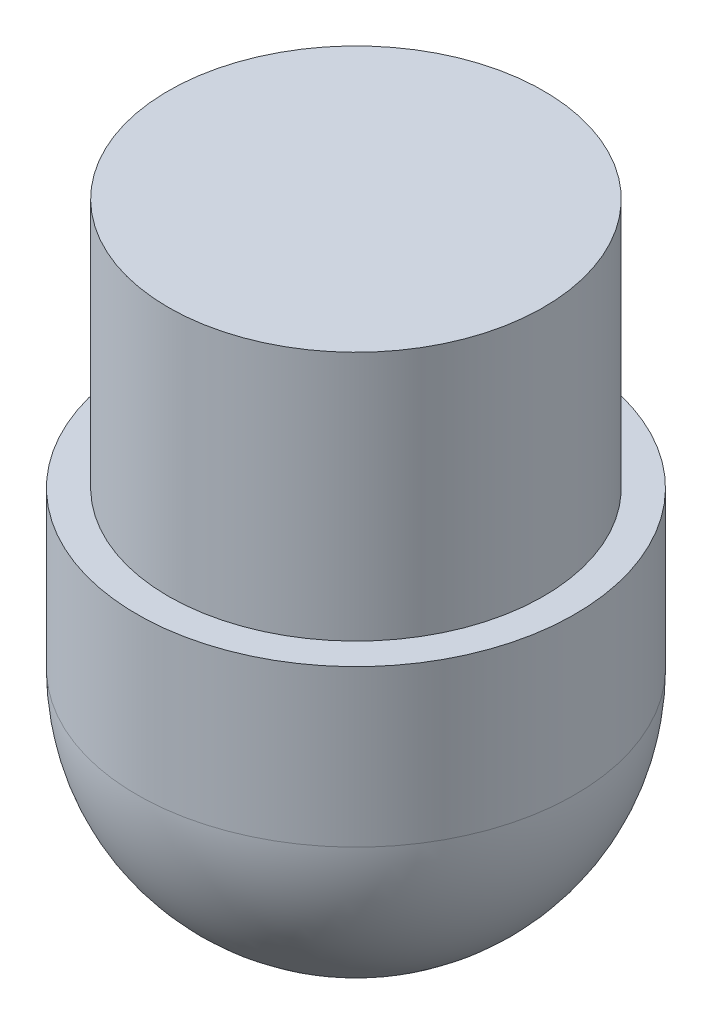
SolidWorks part; units mm, degrees
ref_plane "Front Plane" through (0, 0, 0) normal (0, 0, 1) x (1, 0, 0)
ref_plane "Top Plane" through (0, 0, 0) normal (0, 1, 0) x (1, 0, 0)
ref_plane "Right Plane" through (0, 0, 0) normal (1, 0, 0) x (0, 0, -1)
sketch "Sketch1" plane through (0, 0, 0) normal (0, 1, 0) x (1, 0, 0)
  circle A0 centre (0, 0) radius 15
  dimension "D1" = 30
extrude "Boss-Extrude1" add sketch "Sketch1" along normal blind 20
sketch "Sketch2" plane through (0, 0, 0) normal (0, -1, 0) x (1, 0, 0)
  circle A0 centre (0, 0) radius 17.5
  dimension "D1" = 35
extrude "Boss-Extrude2" add sketch "Sketch2" along normal blind 12.5
dome "Dome1" faces to dome 1 distance 17.5 reverse direction no elliptical dome no face at (0, -12.5, -17.5) parameters "D1"=17.5
